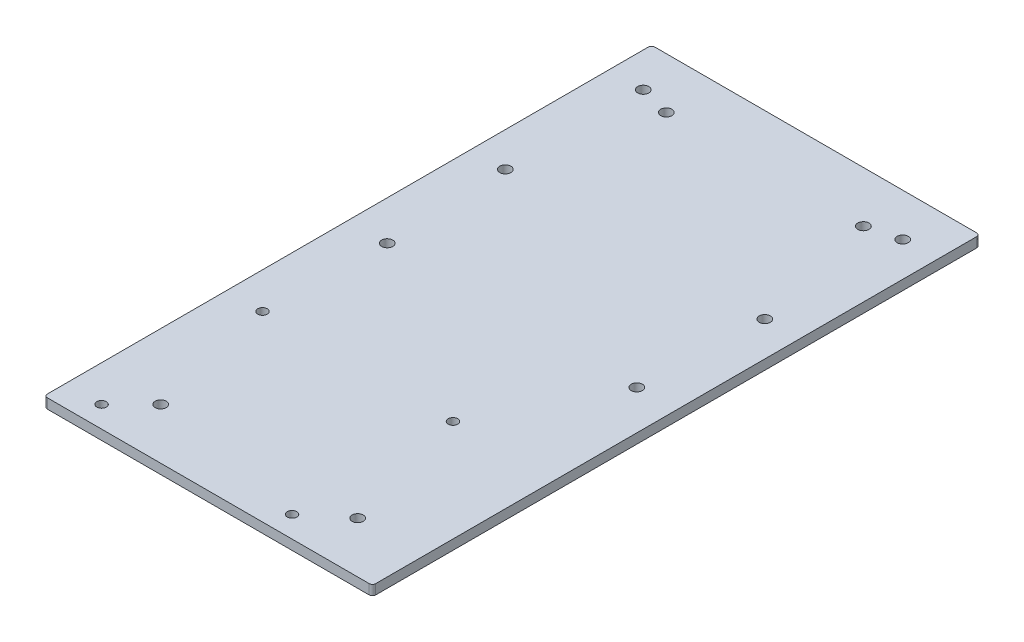
SolidWorks part; units mm, degrees
ref_plane "Front Plane" through (0, 0, 0) normal (0, 0, 1) x (1, 0, 0)
ref_plane "Top Plane" through (0, 0, 0) normal (0, 1, 0) x (1, 0, 0)
ref_plane "Right Plane" through (0, 0, 0) normal (1, 0, 0) x (0, 0, -1)
sketch "Sketch1" plane through (0, 0, 0) normal (0, 1, 0) x (1, 0, 0)
  line L1 (-50, 92.5) -> (50, 92.5)
  line L2 (-50, 92.5) -> (-50, -92.5)
  line L3 (-50, -92.5) -> (50, -92.5)
  line L4 (50, 92.5) -> (50, -92.5)
  line L5 (-50, 92.5) -> (50, -92.5) construction
  line L6 (-50, -92.5) -> (50, 92.5) construction
  point P0 (0, 0)
  dimension "D1" = 100
  dimension "D2" = 185
extrude "plate" add sketch "Sketch1" along normal blind 3
sketch "Sketch2" plane through (0, 3, 0) normal (0, 1, 0) x (1, 0, 0)
  line L0 (-30, 77) -> (30, 77) construction
  line L1 (-30, 77) -> (-30, -77) construction
  circle A0 centre (30, 77) radius 1.7
  circle A1 centre (-30, 77) radius 1.7
  circle A2 centre (30, -77) radius 1.7
  circle A3 centre (-30, -77) radius 1.7
  point P8 (-30, 0)
  point P9 (0, 77)
  dimension "D1" = 3.4
  dimension "D2" = 30
  dimension "D3" = 77
extrude "standoff-holes" cut sketch "Sketch2" against normal up to next
sketch "Sketch3" plane through (0, 3, 0) normal (0, 1, 0) x (1, 0, 0)
  line L0 (-38, 0) -> (38, 0) construction
  circle A0 centre (38, 0) radius 1.7
  circle A1 centre (-38, 0) radius 1.7
  point P4 (0, 0)
  dimension "D1" = 3.4
  dimension "D2" = 76
extrude "power-board-holes" cut sketch "Sketch3" against normal up to next
fillet "Fillet1" radius 1 4 edges at (-50, 1.5, -92.5) (50, 1.5, -92.5) (50, 1.5, 92.5) (-50, 1.5, 92.5)
hole_wizard "M2.5 Clearance Hole1" positions "Sketch8" profile "Sketch9" hole size "M2.5" standard "AS" end condition up to next
sketch "Sketch8" plane through (0, 3, 0) normal (0, 1, 0) x (1, 0, 0)
  point P0 (-39, -85.98)
  point P3 (19, -85.98)
  point P6 (-39, -36.98)
  point P9 (19, -36.98)
sketch "Sketch9" plane through (-39, 3, 85.98) normal (1, 0, 0) x (0, 0, 1)
  line L0 (0, 0) -> (0, 3)
  line L1 (0, 3) -> (1.45, 3)
  line L2 (1.45, 3) -> (1.45, 0)
  line L5 (1.45, 0) -> (0, 0)
  line L11 (0, -6.35) -> (0, 107.95) construction
  dimension "Thru Hole Dia." = 2.9
  dimension "Thru Hole Depth" = 3
hole_wizard "M3 Clearance Hole2" positions "Sketch10" profile "Sketch11" hole size "M3" standard "AS" end condition up to next
sketch "Sketch10" plane through (0, 3, 0) normal (0, 1, 0) x (1, 0, 0)
  point P0 (-39.5, 79.48)
  point P3 (-39.5, 37.48)
  point P6 (39.5, 37.48)
  point P9 (39.5, 79.48)
sketch "Sketch11" plane through (-39.5, 3, -79.48) normal (1, 0, 0) x (0, 0, 1)
  line L0 (0, 0) -> (0, 3)
  line L1 (0, 3) -> (1.7, 3)
  line L2 (1.7, 3) -> (1.7, 0)
  line L5 (1.7, 0) -> (0, 0)
  line L11 (0, -6.35) -> (0, 107.95) construction
  dimension "Thru Hole Dia." = 3.4
  dimension "Thru Hole Depth" = 3
